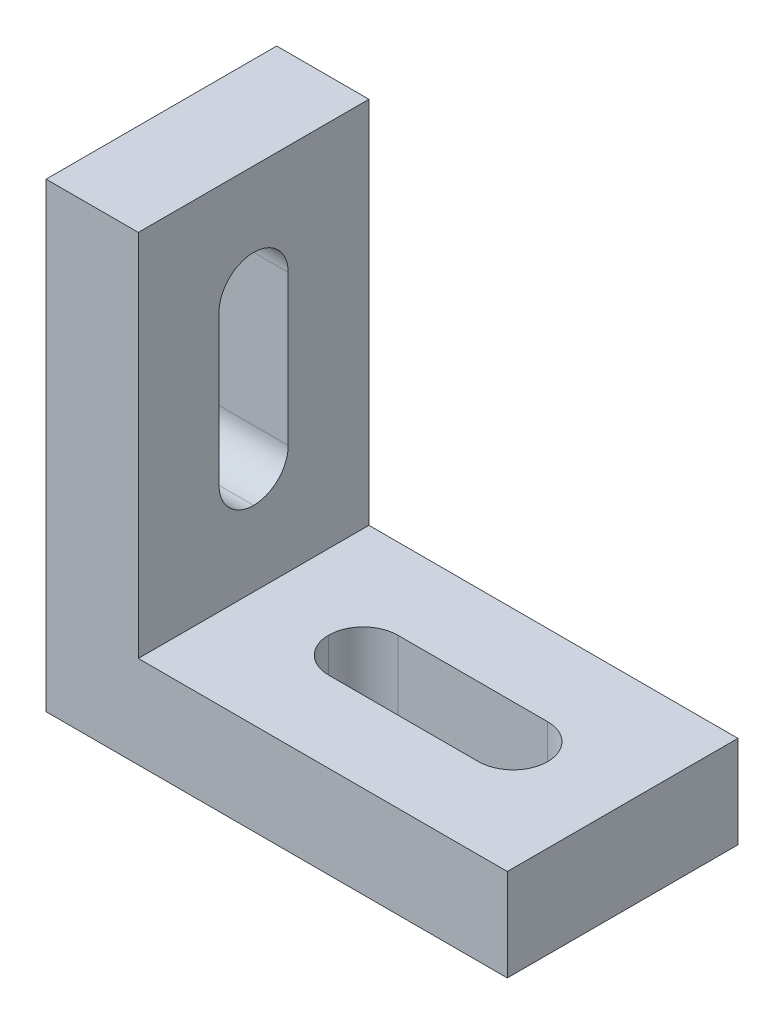
SolidWorks part; units mm, degrees
ref_plane "Front Plane" through (0, 0, 0) normal (0, 0, 1) x (1, 0, 0)
ref_plane "Top Plane" through (0, 0, 0) normal (0, 1, 0) x (1, 0, 0)
ref_plane "Right Plane" through (0, 0, 0) normal (1, 0, 0) x (0, 0, -1)
sketch "Sketch1" plane through (0, 0, 0) normal (0, 0, 1) x (1, 0, 0)
  line L0 (4, -20) -> (36, -20)
  line L1 (-4, 20) -> (4, 20)
  line L2 (-4, 20) -> (-4, -20)
  line L3 (-4, -20) -> (4, -20)
  line L4 (4, 20) -> (4, -12)
  line L5 (-4, 20) -> (4, -20) construction
  line L6 (-4, -20) -> (4, 20) construction
  line L7 (36, -20) -> (36, -12)
  line L8 (36, -12) -> (4, -12)
  point P0 (0, 0)
  dimension "D1" = 8
  dimension "D2" = 40
  dimension "D3" = 40
  dimension "D4" = 8
extrude "Boss-Extrude1" add sketch "Sketch1" along normal blind 20
sketch "Sketch2" plane through (0, -12, 0) normal (0, 1, 0) x (1, 0, 0)
  line L0 (4, -10) -> (36, -10) construction
  line L1 (4, -20) -> (4, 0) construction
  line L2 (36, -20) -> (36, 0) construction
  line L3 (20, 0) -> (20, -20) construction
  line L4 (36, 0) -> (4, 0) construction
  line L5 (36, -20) -> (4, -20) construction
  line L7 (29.5, -13) -> (10.5, -13)
  line L8 (29.5, -13) -> (29.5, -7)
  line L9 (29.5, -7) -> (10.5, -7)
  line L10 (10.5, -13) -> (10.5, -7)
  line L11 (29.5, -13) -> (10.5, -7) construction
  line L12 (29.5, -7) -> (10.5, -13) construction
  point P12 (20, -10)
  dimension "D1" = 19
  dimension "D2" = 6
extrude "Cut-Extrude1" cut sketch "Sketch2" against normal blind 20
sketch "Sketch3" plane through (4, 0, 0) normal (1, 0, 0) x (0, 0, -1)
  line L0 (-10, 20) -> (-10, -12) construction
  line L1 (-20, 20) -> (0, 20) construction
  line L2 (-20, -12) -> (0, -12) construction
  line L3 (-20, 4) -> (0, 4) construction
  line L4 (-20, -12) -> (-20, 20) construction
  line L5 (0, -12) -> (0, 20) construction
  line L7 (-13, -5.5) -> (-7, -5.5)
  line L8 (-13, -5.5) -> (-13, 13.5)
  line L9 (-13, 13.5) -> (-7, 13.5)
  line L10 (-7, -5.5) -> (-7, 13.5)
  line L11 (-13, -5.5) -> (-7, 13.5) construction
  line L12 (-13, 13.5) -> (-7, -5.5) construction
  point P12 (-10, 4)
  dimension "D1" = 6
  dimension "D2" = 19
extrude "Cut-Extrude2" cut sketch "Sketch3" against normal blind 20
fillet "Fillet1" radius 3 8 edges at (29.5, -16, 7) (29.5, -16, 13) (10.5, -16, 7) (10.5, -16, 13) (0, -5.5, 13) (0, -5.5, 7) (0, 13.5, 13) (0, 13.5, 7)
